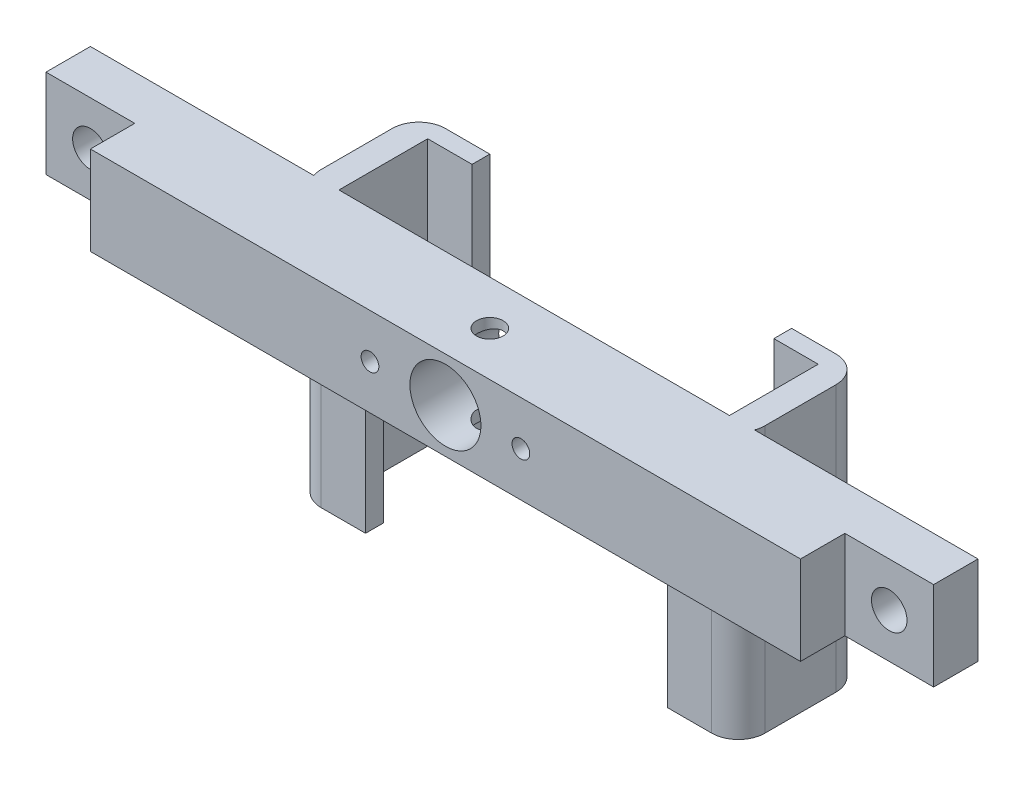
SolidWorks part; units mm, degrees
ref_plane "Front Plane" through (0, 0, 0) normal (0, 0, 1) x (1, 0, 0)
ref_plane "Top Plane" through (0, 0, 0) normal (0, 1, 0) x (1, 0, 0)
ref_plane "Right Plane" through (0, 0, 0) normal (1, 0, 0) x (0, 0, -1)
sketch "Sketch1" plane through (0, 0, 0) normal (0, 0, 1) x (1, 0, 0)
  line L1 (-50, 5) -> (50, 5)
  line L2 (-50, 5) -> (-50, -5)
  line L3 (-50, -5) -> (50, -5)
  line L4 (50, 5) -> (50, -5)
  line L5 (-50, 5) -> (50, -5) construction
  line L6 (-50, -5) -> (50, 5) construction
  point P0 (0, 0)
  dimension "D1" = 100
  dimension "D2" = 10
extrude "Boss-Extrude1" add sketch "Sketch1" along normal blind 10
sketch "Sketch2" plane through (0, 5, 0) normal (0, 1, 0) x (1, 0, 0)
  line L5 (-50, -10) -> (-40, -10)
  line L6 (-50, -10) -> (-50, -5)
  line L7 (-50, -5) -> (-40, -5)
  line L8 (-40, -10) -> (-40, -5)
  dimension "D1" = 10
  dimension "D2" = 5
sketch "Sketch6" plane through (0, 0, 0) normal (0, 0, -1) x (-1, 0, 0)
  line L0 (0, 5) -> (0, -5) construction
  line L1 (-25, 5) -> (-25, -5)
  line L3 (-25, 5) -> (-22, 5)
  line L4 (-50, 5) -> (-50, -5)
  line L5 (-50, -5) -> (50, -5)
  line L6 (-50, 5) -> (-50, -5)
  line L7 (50, 5) -> (-50, 5)
  line L9 (-50, -5) -> (50, -5)
  line L11 (50, 5) -> (-50, 5)
  line L12 (-22, 5) -> (-22, -5)
  line L13 (-22, -5) -> (-25, -5)
  line L17 (50, -5) -> (50, 5)
  line L18 (50, -5) -> (50, 5)
  line M11 (-50, -5) -> (50, -5)
  line M13 (50, 5) -> (-50, 5)
  dimension "D2" = 25
  dimension "D3" = 3
  dimension "D1" = 0
extrude "Boss-Extrude2" add sketch "Sketch6" along normal blind 12 contours L12 L1 M13 M11 region at (23.5, 0, 0)
sketch "Sketch8" plane through (22, 0, 0) normal (-1, 0, 0) x (0, 0, 1)
  line L0 (-12, -5) -> (0, -5) construction
  line L1 (-12, 5) -> (-10, 5)
  line L2 (-12, 5) -> (-12, -5)
  line L3 (-12, -5) -> (-10, -5)
  line L4 (-10, 5) -> (-10, -5)
  dimension "D1" = 2
extrude "Boss-Extrude3" add sketch "Sketch8" along normal blind 5
sketch "Sketch9" plane through (0, -5, 0) normal (0, -1, 0) x (1, 0, 0)
  line L0 (17, -12) -> (17, 0) construction
  line L1 (-50, 0) -> (22, 0) construction
  line L2 (17, 0) -> (22, 0)
  line L4 (17, 0) -> (17, 2)
  line L5 (17, 2) -> (25, 2)
  line L6 (25, 0) -> (25, 2)
  line L7 (22, 0) -> (22, -10)
  line L8 (22, -10) -> (17, -10)
  line L9 (17, -10) -> (17, -12)
  line L10 (17, -12) -> (25, -12)
  line L11 (25, -12) -> (25, 0)
  line L12 (25, 0) -> (25, 2)
  line L13 (-50, 10) -> (-50, 0) construction
  line L14 (-50, 10) -> (50, 10) construction
  line M16 (-50, 0) -> (22, 0)
  line M17 (22, 0) -> (22, -10)
  line M18 (22, -10) -> (17, -10)
  line M19 (17, -10) -> (17, -12)
  line M20 (17, -12) -> (25, -12)
  line M21 (25, -12) -> (25, 0)
  dimension "D1" = 8
  dimension "D2" = 2
  dimension "D3" = 2
extrude "Boss-Extrude4" add sketch "Sketch9" along normal blind 20 contours L6 L5 L4 M21 M16 M17 M18 M19 M20 region at (22.2097, -5, -5)
mirror "Mirror3" about plane through (0, 0, 0) normal (1, 0, 0) of "Boss-Extrude4", "Boss-Extrude3", "Boss-Extrude2"
extrude "Cut-Extrude1" cut sketch "Sketch2" against normal blind 10
mirror "Mirror4" about plane through (0, 0, 0) normal (1, 0, 0) of "Cut-Extrude1"
sketch "Sketch10" plane through (0, 0, 5) normal (0, 0, 1) x (1, 0, 0)
  line L0 (50, -5) -> (50, 5) construction
  line L1 (40, -5) -> (50, -5) construction
  circle A0 centre (45, 0) radius 2
  dimension "D1" = 4
  dimension "D2" = 5
  dimension "D3" = 5
extrude "Cut-Extrude2" cut sketch "Sketch10" against normal up to next
mirror "Mirror5" about plane through (0, 0, 0) normal (1, 0, 0) of "Cut-Extrude2"
sketch "Sketch12" plane through (0, 0, 0) normal (0, 0, -1) x (-1, 0, 0)
  line L0 (0, 5) -> (0, -5) construction
  line L1 (-22, 5) -> (22, 5) construction
  line L2 (17, -5) -> (-17, -5) construction
sketch "Sketch13" plane through (0, 0, 0) normal (0, 0, -1) x (-1, 0, 0)
  line L0 (0, 0) -> (-8.5, 0) construction
  line L1 (0, 0) -> (8.5, 0) construction
  circle A0 centre (0, 0) radius 4
  circle A1 centre (-8.5, 0) radius 1
  circle A2 centre (8.5, 0) radius 1
  dimension "D1" = 8
  dimension "D4" = 2
  dimension "D5" = 2
  dimension "D2" = 8.5
  dimension "D3" = 8.5
extrude "Cut-Extrude3" cut sketch "Sketch13" against normal through all
fillet "Fillet1" radius 3 2 edges at (25, -10, -12) (-25, -10, -12)
fillet "Fillet2" radius 3 2 edges at (-25, -15, 2) (25, -15, 2)
sketch "Sketch14" plane through (0, 5, 0) normal (0, 1, 0) x (1, 0, 0)
  circle A0 centre (0, -5) radius 1.5
  point P2 (0, 0)
  dimension "D1" = 3
  dimension "D2" = 5
extrude "Cut-Extrude4" cut sketch "Sketch14" against normal blind 10
